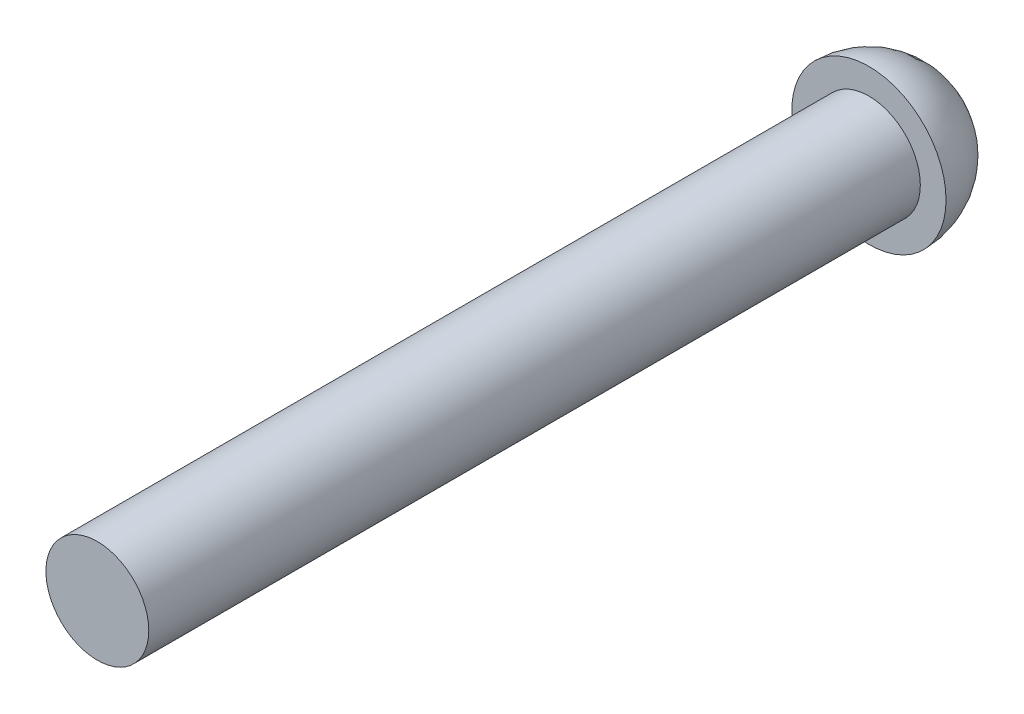
SolidWorks part; units mm, degrees
ref_plane "Plan de face" through (0, 0, 0) normal (0, 0, 1) x (1, 0, 0)
ref_plane "Plan de dessus" through (0, 0, 0) normal (0, 1, 0) x (1, 0, 0)
ref_plane "Plan de droite" through (0, 0, 0) normal (1, 0, 0) x (0, 0, -1)
sketch "Esquisse1" plane through (0, 0, 0) normal (0, 0, 1) x (1, 0, 0)
  circle A0 centre (0, 0) radius 1
extrude "Boss.-Extru.1" add sketch "Esquisse1" along normal blind 15
sketch "Esquisse2" plane through (0, 0, 0) normal (0, 1, 0) x (1, 0, 0)
  line L0 (0, 0) -> (0, 1.5)
  line L1 (0, 0) -> (1.5, 0)
  arc A0 (0, 1.5) -> (1.5, 0) centre (0, 0) cw
  point P4 (0, 0)
  dimension "D1" = 1.5
revolve "Révolution1" add sketch "Esquisse2" angle 360 about L0
sketch "Esquisse4" plane through (0, 0, 0) normal (0, 1, 0) x (1, 0, 0)
  line L1 (-0.0839, 2.1555) -> (0.0839, 2.1555)
  line L2 (-0.0839, 2.1555) -> (-0.0839, 0.8445)
  line L3 (-0.0839, 0.8445) -> (0.0839, 0.8445)
  line L4 (0.0839, 2.1555) -> (0.0839, 0.8445)
  line L5 (-0.0839, 2.1555) -> (0.0839, 0.8445) construction
  line L6 (-0.0839, 0.8445) -> (0.0839, 2.1555) construction
  arc A0 (1.5, 0) -> (-1.5, 0) centre (0, 0) ccw construction
  point P0 (0, 1.5)
extrude "Enlèv. mat.-Extru.1" cut sketch "Esquisse4" against normal blind 10 and the other way blind 10
